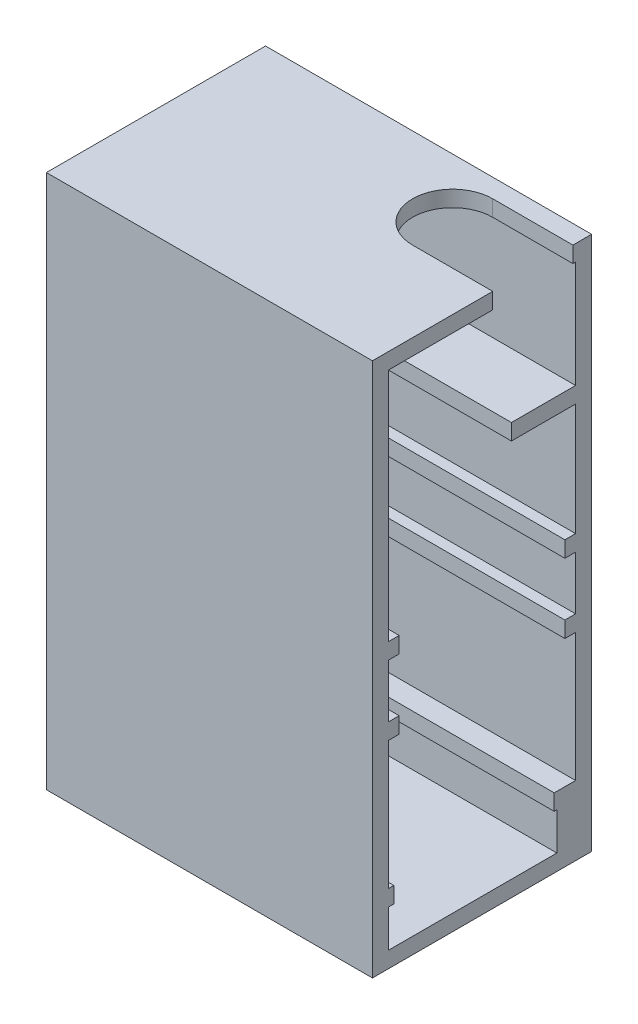
SolidWorks part; units mm, degrees
ref_plane "Plan de face" through (0, 0, 0) normal (0, 0, 1) x (1, 0, 0)
ref_plane "Plan de dessus" through (0, 0, 0) normal (0, 1, 0) x (1, 0, 0)
ref_plane "Plan de droite" through (0, 0, 0) normal (1, 0, 0) x (0, 0, -1)
sketch "Esquisse1" plane through (0, 0, 0) normal (0, 1, 0) x (1, 0, 0)
  line L1 (-30.5, -20.5) -> (30.5, -20.5)
  line L2 (-30.5, -20.5) -> (-30.5, 20.5)
  line L3 (-30.5, 20.5) -> (30.5, 20.5)
  line L4 (30.5, -20.5) -> (30.5, 20.5)
  line L5 (-30.5, -20.5) -> (30.5, 20.5) construction
  line L6 (-30.5, 20.5) -> (30.5, -20.5) construction
  point P0 (0, 0)
  dimension "D1" = 61
  dimension "D2" = 41
extrude "Boss.-Extru.1" add sketch "Esquisse1" along normal blind 100
sketch "Esquisse3" plane through (30.5, 0, 0) normal (1, 0, 0) x (0, 0, -1)
  line L0 (-20.5, 100) -> (20.5, 0) construction
  line L1 (17.5, 13) -> (17.5, 97)
  line L2 (14, 3) -> (-17.5, 3)
  line L4 (17.5, 97) -> (-17.5, 97)
  line L5 (-17.5, 3) -> (-17.5, 97)
  line L6 (17.5, 3) -> (-17.5, 97) construction
  line L7 (17.5, 97) -> (-17.5, 3) construction
  line L8 (-20.5, 100) -> (20.5, 100) construction
  line L14 (17.5, 13) -> (14, 13)
  line L15 (14, 3) -> (14, 13)
  point P4 (0, 50)
  point P5 (0, 50)
  dimension "D1" = 3
  dimension "D3" = 3.5
  dimension "D4" = 10
extrude "Enlèv. mat.-Extru.1" cut sketch "Esquisse3" against normal blind 57 contours L4 L5 L2 L15 L14 L1
sketch "Esquisse6" plane through (0, 0, -20.5) normal (0, 0, -1) x (-1, 0, 0)
  line L0 (-30.5, 100) -> (-30.5, 0) construction
  line L1 (-30.5, 10) -> (27.5, 10)
  line L2 (-30.5, 10) -> (-30.5, 13)
  line L3 (-30.5, 13) -> (27.5, 13)
  line L4 (27.5, 10) -> (27.5, 13)
  line L5 (30.5, 100) -> (30.5, 0) construction
  line L6 (-30.5, 0) -> (30.5, 0) construction
  dimension "D1" = 3
  dimension "D2" = 3
  dimension "D3" = 10
extrude "Boss.-Extru.2" add sketch "Esquisse6" against normal blind 4
mirror "Symétrie1" about plane through (0, 0, 0) normal (0, 0, 1) of "Boss.-Extru.2"
sketch "Esquisse7" plane through (-30.5, 0, 0) normal (-1, 0, 0) x (0, 0, 1)
  line L0 (-20.5, 100) -> (-20.5, 0) construction
  line L1 (-17.5, 10) -> (17.5, 10)
  line L2 (-17.5, 10) -> (-17.5, 13)
  line L3 (-17.5, 13) -> (17.5, 13)
  line L4 (17.5, 10) -> (17.5, 13)
  line L5 (-20.5, 0) -> (20.5, 0) construction
  line L6 (20.5, 100) -> (20.5, 0) construction
  dimension "D1" = 3
  dimension "D2" = 3
  dimension "D3" = 10
  dimension "D4" = 3
extrude "Boss.-Extru.3" add sketch "Esquisse7" against normal blind 6
sketch "Esquisse11" plane through (0, 0, -20.5) normal (0, 0, -1) x (-1, 0, 0)
  line L0 (-30.5, 100) -> (-30.5, 0) construction
  line L1 (-30.5, 10) -> (27.5, 10)
  line L2 (-30.5, 10) -> (-30.5, 13)
  line L3 (-30.5, 13) -> (27.5, 13)
  line L4 (27.5, 10) -> (27.5, 13)
  line L5 (30.5, 100) -> (30.5, 0) construction
  line L6 (-30.5, 0) -> (30.5, 0) construction
  dimension "D1" = 0
  dimension "D2" = 3
  dimension "D3" = 3
  dimension "D4" = 10
extrude "Boss.-Extru.4" add sketch "Esquisse11" against normal blind 7
sketch "Esquisse12" plane through (0, 0, -20.5) normal (0, 0, -1) x (-1, 0, 0)
  line L0 (-30.5, 100) -> (-30.5, 0) construction
  line L1 (-30.5, 50) -> (29.0466, 50)
  line L2 (-30.5, 50) -> (-30.5, 53)
  line L3 (-30.5, 53) -> (29.0466, 53)
  line L4 (29.0466, 50) -> (29.0466, 53)
  line L5 (-30.5, 0) -> (30.5, 0) construction
  dimension "D1" = 3
  dimension "D2" = 50
extrude "Boss.-Extru.5" add sketch "Esquisse12" against normal blind 5
mirror "Symétrie2" about plane through (0, 0, 0) normal (0, 0, 1) of "Boss.-Extru.5"
pattern_linear "Répétition linéaire1" count 2 spacing 13 along (0, -1, 0) of "Symétrie2"
sketch "Esquisse13" plane through (0, 0, 20.5) normal (0, 0, 1) x (1, 0, 0)
  line L0 (-30.5, 100) -> (-30.5, 0) construction
  line L1 (-27.5, 83) -> (-12.5, 83)
  line L2 (-27.5, 83) -> (-27.5, 80)
  line L3 (-27.5, 80) -> (-12.5, 80)
  line L4 (-12.5, 83) -> (-12.5, 80)
  line L5 (-30.5, 100) -> (30.5, 100) construction
  dimension "D1" = 3
  dimension "D2" = 3
  dimension "D3" = 15
  dimension "D4" = 17
extrude "Boss.-Extru.6" add sketch "Esquisse13" against normal blind 5 contours L3 L4 L1 L2
pattern_linear "Répétition linéaire3" count 2 spacing 4 along (0, 1, 0) of "Boss.-Extru.6"
sketch "Esquisse14" plane through (0, 0, -20.5) normal (0, 0, -1) x (-1, 0, 0)
  line L0 (30.5, 100) -> (30.5, 0) construction
  line L1 (27.5, 80) -> (12.5, 80)
  line L2 (27.5, 80) -> (27.5, 87)
  line L3 (27.5, 87) -> (12.5, 87)
  line L4 (12.5, 80) -> (12.5, 87)
  line L6 (-30.5, 100) -> (30.5, 100) construction
  dimension "D1" = 15
  dimension "D2" = 3
  dimension "D3" = 7
  dimension "D4" = 20
extrude "Boss.-Extru.7" add sketch "Esquisse14" against normal blind 16
sketch "Esquisse15" plane through (-12.5, 0, 0) normal (1, 0, 0) x (0, 0, -1)
  line L0 (4.5, 80) -> (4.5, 87) construction
  line L1 (3.5, 83) -> (5.5, 83)
  line L2 (3.5, 83) -> (3.5, 84)
  line L3 (3.5, 84) -> (5.5, 84)
  line L4 (5.5, 83) -> (5.5, 84)
  line L5 (3.5, 83) -> (5.5, 84) construction
  line L6 (3.5, 84) -> (5.5, 83) construction
  point P0 (4.5, 83.5)
  dimension "D1" = 1
  dimension "D2" = 2
extrude "Enlèv. mat.-Extru.2" cut sketch "Esquisse15" against normal up to surface (14 mm away) up to face at (-26.5, 60.6875, 2.75)
sketch "Esquisse16" plane through (0, 100, 0) normal (0, 1, 0) x (1, 0, 0)
  line L1 (30.5, 20.5) -> (-30.5, 20.5) construction
  line L2 (30.5, -20.5) -> (30.5, 20.5) construction
  line L3 (15.5, 2) -> (30.5, 2)
  line L4 (15.5, 17) -> (30.5, 17)
  line L5 (30.5, 2) -> (30.5, 17)
  arc A0 (15.5, 17) -> (15.5, 2) centre (15.5, 9.5) ccw
  dimension "D1" = 15
  dimension "D2" = 15
  dimension "D3" = 11
extrude "Enlèv. mat.-Extru.3" cut sketch "Esquisse16" against normal blind 15
sketch "Esquisse17" plane through (0, 0, -20.5) normal (0, 0, -1) x (-1, 0, 0)
  line L0 (-30.5, 100) -> (-30.5, 0) construction
  line L1 (-30.5, 74) -> (29.4544, 74)
  line L2 (-30.5, 74) -> (-30.5, 77)
  line L3 (-30.5, 77) -> (29.4544, 77)
  line L4 (29.4544, 74) -> (29.4544, 77)
  line L5 (-30.5, 100) -> (30.5, 100) construction
  dimension "D1" = 3
  dimension "D2" = 23
extrude "Boss.-Extru.8" add sketch "Esquisse17" against normal blind 15
